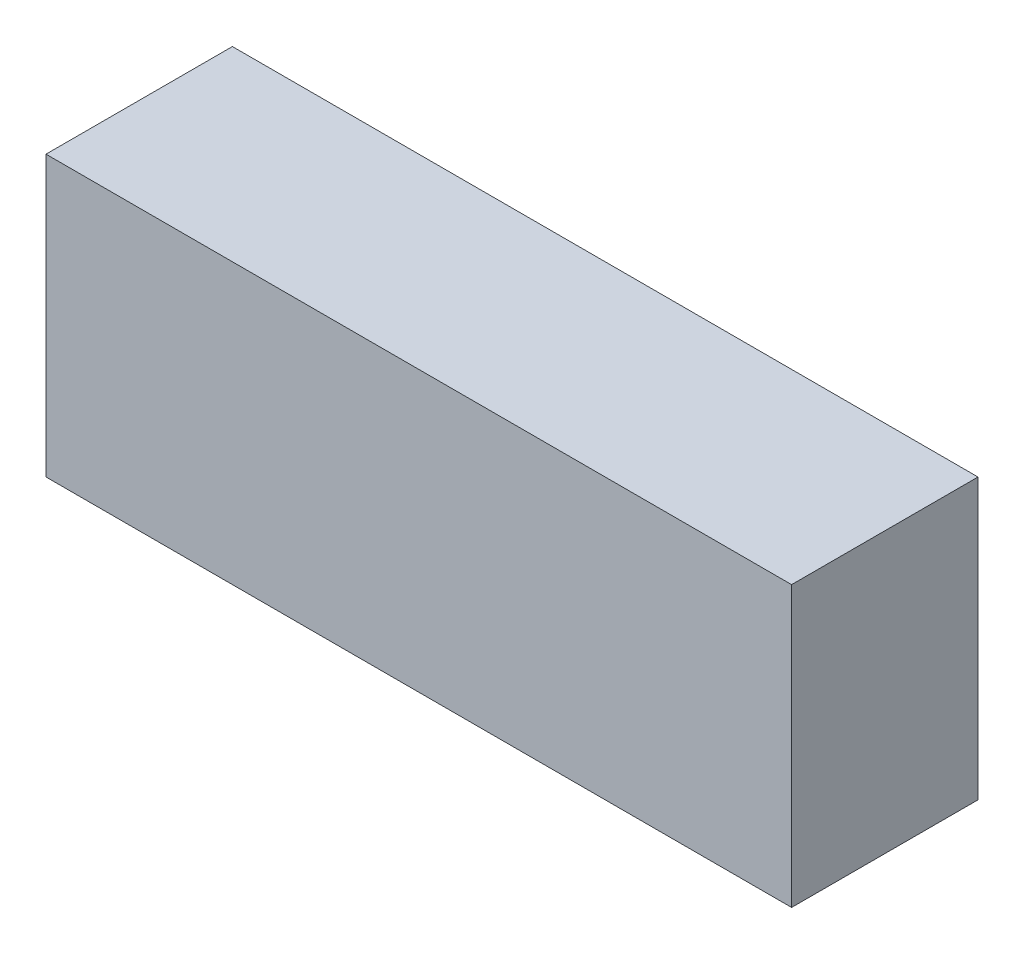
SolidWorks part; units mm, degrees
ref_plane "前视基准面" through (0, 0, 0) normal (0, 0, 1) x (1, 0, 0)
ref_plane "上视基准面" through (0, 0, 0) normal (0, 1, 0) x (1, 0, 0)
ref_plane "右视基准面" through (0, 0, 0) normal (1, 0, 0) x (0, 0, -1)
other "Configuration Table"
sketch "Sketch1" plane through (0, 0, 0) normal (0, 1, 0) x (1, 0, 0)
  line L1 (-40, -10) -> (40, -10)
  line L2 (-40, -10) -> (-40, 10)
  line L3 (-40, 10) -> (40, 10)
  line L4 (40, -10) -> (40, 10)
  line L5 (-40, -10) -> (40, 10) construction
  line L6 (-40, 10) -> (40, -10) construction
  point P0 (0, 0)
extrude "Boss-Extrude1" add sketch "Sketch1" along normal blind 30
sketch3d "3DSketch1"
  line L0 (-25, 0, 0) -> (-25, 100, 0) construction
ref_axis "Axis_Finger_L" through (-25, 0, 0) along (0, 1, 0)
sketch3d "3DSketch2"
  line L0 (25, 0, 0) -> (25, 100, 0) construction
ref_axis "Axis_Finger_R" through (25, 0, 0) along (0, 1, 0)
sketch3d "3DSketch3"
  line L0 (0, 0, -100) -> (0, 0, 100) construction
ref_axis "Axis_J5" through (0, 0, -100) along (0, 0, 1)
ref_plane "Mate_Top" through (0, 30, 0) normal (0, 1, 0) x (1, 0, 0)
ref_plane "Mate_Mid" through (0, 0, 0) normal (0, 0, 1) x (1, 0, 0)
